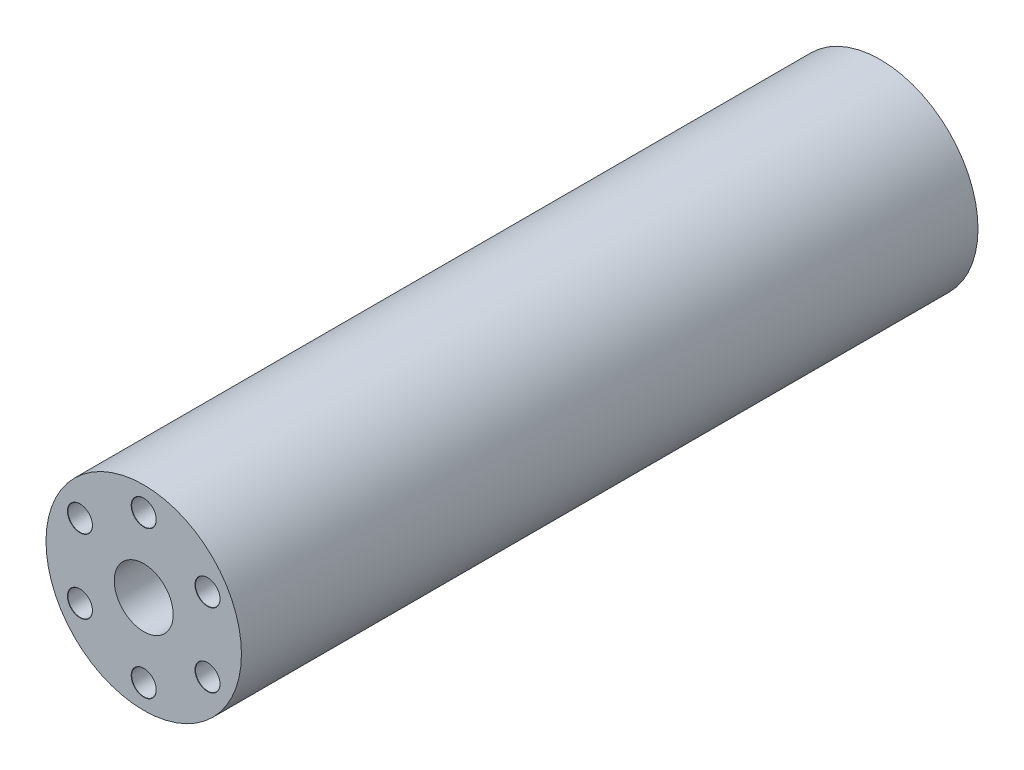
SolidWorks part; units mm, degrees
material "Alloy Steel"
ref_plane "Front Plane" through (0, 0, 0) normal (0, 0, 1) x (1, 0, 0)
ref_plane "Top Plane" through (0, 0, 0) normal (0, 1, 0) x (1, 0, 0)
ref_plane "Right Plane" through (0, 0, 0) normal (1, 0, 0) x (0, 0, -1)
sketch "Sketch1" plane through (0, 0, 0) normal (0, 0, 1) x (1, 0, 0)
  circle A0 centre (0, 0) radius 9.95
  dimension "D1" = 19.9
extrude "Boss-Extrude1" add sketch "Sketch1" along normal blind 75
sketch "Sketch2" plane through (0, 0, 0) normal (0, 0, 1) x (1, 0, 0)
  point P0 (0, 0)
hole_wizard "Ø6.0mm Dowel Hole1" positions "Sketch2" profile "Sketch4" hole size "Ø6.0" standard "DIN" end condition through all
sketch "Sketch4" plane through (0, 0, 0) normal (1, 0, 0) x (0, 1, 0)
  line L0 (0, 0) -> (0, 75)
  line L1 (0, 75) -> (3, 75)
  line L2 (3, 75) -> (3, 0)
  line L5 (3, 0) -> (0, 0)
  line L11 (0, -6.35) -> (0, 107.95) construction
  dimension "Thru Hole Dia." = 6
  dimension "Thru Hole Depth" = 75
sketch "Sketch5" plane through (0, 0, 0) normal (0, 0, -1) x (-1, 0, 0)
  circle A0 centre (0, 0) radius 7
  point P6 (0, 7)
  point P10 (6.0622, -3.5)
  point P11 (-6.0622, -3.5)
  dimension "D1" = 14
  dimension "D2" = 3
hole_wizard "Tap Drill for M3 Tap1" positions "Sketch5" profile "Sketch6" hole size "M3" standard "DIN"
sketch "Sketch6" plane through (6.0622, -3.5, 0) normal (1, 0, 0) x (0, 1, 0)
  line L0 (0, 0) -> (0, 10.7511)
  line L1 (0, 10.7511) -> (1.25, 10)
  line L2 (1.25, 10) -> (1.25, 0.025)
  line L3 (1.25, 0.025) -> (1.275, 0)
  line L5 (1.275, 0) -> (0, 0)
  line L6 (-1.25, 0.025) -> (-1.275, 0) construction
  line L10 (0, 10.7511) -> (-1.25, 10) construction
  line L11 (0, -6.35) -> (0, 107.95) construction
  dimension "Hole Dia." = 2.5
  dimension "Hole Depth" = 10
  dimension "Near C'Sink Dia." = 2.55
  dimension "Near C'Sink Angle" = 90
  dimension "Drill Angle" = 118
sketch "Sketch7" plane through (0, 0, 75) normal (0, 0, 1) x (1, 0, 0)
  line L0 (0, 3) -> (0, 12) construction
  circle A0 centre (0, 0) radius 3 construction
  circle A2 centre (0, 0) radius 12 construction
  circle A4 centre (0, 0) radius 7.5 construction
  point P20 (0, 7.5)
  point P24 (6.4952, 3.75)
  point P25 (6.4952, -3.75)
  point P26 (0, -7.5)
  point P27 (-6.4952, -3.75)
  point P28 (-6.4952, 3.75)
  dimension "D1" = 15
  dimension "D2" = 6
hole_wizard "Tap Drill for M3 Tap2" positions "Sketch7" profile "Sketch9" hole size "M3" standard "DIN"
sketch "Sketch9" plane through (-6.4952, 3.75, 75) normal (1, 0, 0) x (0, -1, 0)
  line L0 (0, 0) -> (0, 10.7511)
  line L1 (0, 10.7511) -> (1.25, 10)
  line L2 (1.25, 10) -> (1.25, 0.025)
  line L3 (1.25, 0.025) -> (1.275, 0)
  line L5 (1.275, 0) -> (0, 0)
  line L6 (-1.25, 0.025) -> (-1.275, 0) construction
  line L10 (0, 10.7511) -> (-1.25, 10) construction
  line L11 (0, -6.35) -> (0, 107.95) construction
  dimension "Hole Dia." = 2.5
  dimension "Hole Depth" = 10
  dimension "Near C'Sink Dia." = 2.55
  dimension "Near C'Sink Angle" = 90
  dimension "Drill Angle" = 118
